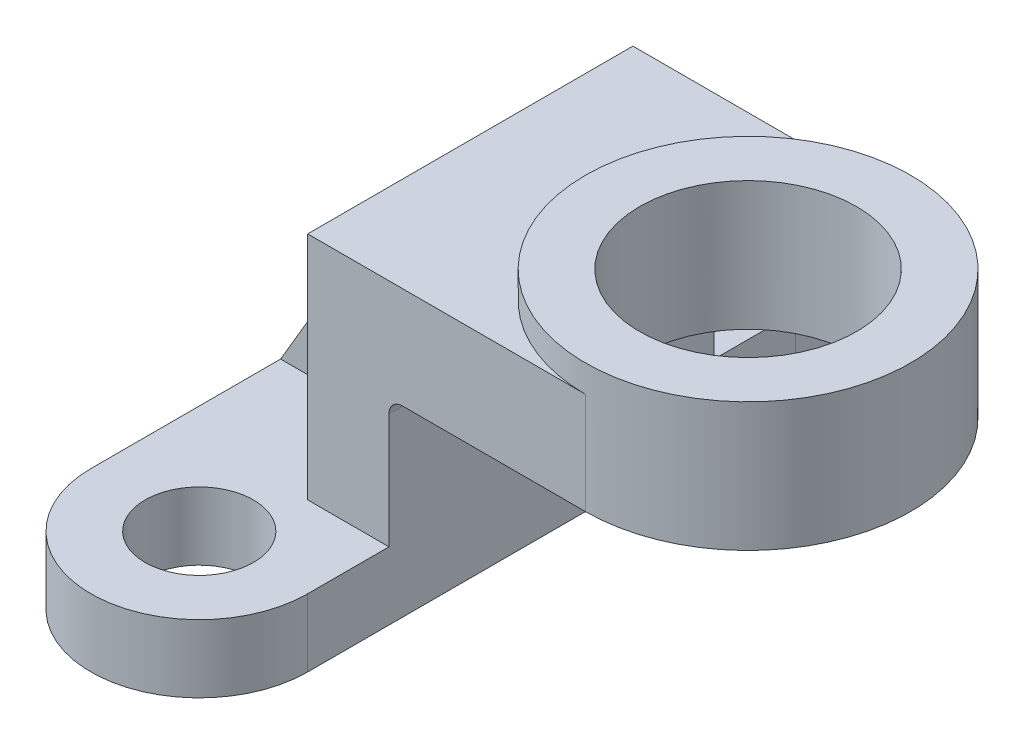
SolidWorks part; units mm, degrees
ref_plane "Front Plane" through (0, 0, 0) normal (0, 0, 1) x (1, 0, 0)
ref_plane "Top Plane" through (0, 0, 0) normal (0, 1, 0) x (1, 0, 0)
ref_plane "Right Plane" through (0, 0, 0) normal (1, 0, 0) x (0, 0, -1)
sketch "Sketch2" plane through (0, 0, 0) normal (0, 1, 0) x (1, 0, 0)
  line L0 (-16, 36) -> (-16, -36)
  line L1 (16, 36) -> (16, -36)
  line L2 (-16, 0) -> (16, 0) construction
  circle A0 centre (0, 36) radius 16
  circle A1 centre (0, -36) radius 16
  circle A2 centre (0, -36) radius 8
  circle A3 centre (0, 36) radius 8
  point P11 (0, 0)
  point P14 (0, 0)
  point P15 (0, 0)
  dimension "D1" = 16
  dimension "D2" = 16
  dimension "D3" = 32
  dimension "D4" = 32
  dimension "D5" = 72
extrude "Boss-Extrude1" add sketch "Sketch2" along normal blind 10 contours A0 A3 | L2 L0 A1 L1 | L0 L2 L1 A0 | A1 A2 region at (0, 0, -11.9889) region at (0, 0, -51.5475) region at (0, 0, 11.9889) region at (0, 0, 20.4525)
sketch "Sketch3" plane through (0, 0, 0) normal (0, 0, 1) x (1, 0, 0)
  line L0 (16, 10) -> (16, 27)
  line L1 (18, 29) -> (45, 29)
  line L2 (45, 29) -> (45, 44)
  line L3 (45, 44) -> (4, 44)
  line L4 (4, 44) -> (4, 10)
  line L6 (16, 10) -> (-16, 10) construction
  line L7 (4, 10) -> (16, 10)
  arc A0 (18, 29) -> (16, 27) centre (18, 27) ccw
  point P10 (16, 29)
  dimension "D5" = 2
  dimension "D1" = 41
  dimension "D2" = 15
  dimension "D3" = 19
  dimension "D4" = 12
extrude "Boss-Extrude2" add sketch "Sketch3" along normal blind 24 and the other way blind 24
sketch "Sketch4" plane through (0, 44, 0) normal (0, 1, 0) x (1, 0, 0)
  line L0 (45, 24) -> (45, -24) construction
  circle A0 centre (45, 0) radius 24
  dimension "D1" = 48
extrude "Boss-Extrude3" add sketch "Sketch4" along normal blind 4 and the other way blind 15
sketch "Sketch5" plane through (0, 48, 0) normal (0, 1, 0) x (1, 0, 0)
  circle A0 centre (45, 0) radius 16
  dimension "D1" = 32
extrude "Cut-Extrude1" cut sketch "Sketch5" against normal blind 25 and the other way blind 10
sketch "Sketch8" plane through (0, 0, 0) normal (0, 0, 1) x (1, 0, 0)
  line L0 (4, 44) -> (-16, 10)
rib "Rib8" sketch "Sketch8" sketch "Sketch8" thickness 16 extrusion direction parallel to sketch draft on no parameters "D1"=16
